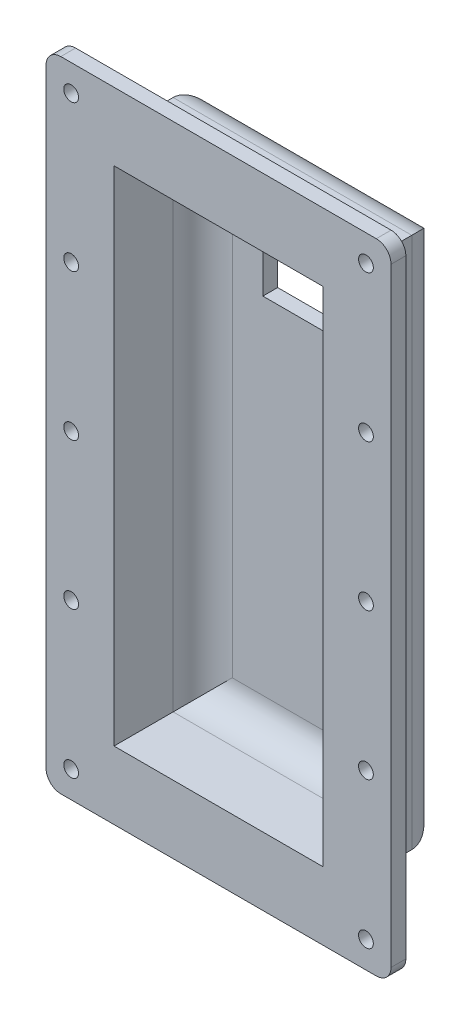
SolidWorks part; units mm, degrees
ref_plane "Front Plane" through (0, 0, 0) normal (0, 0, 1) x (1, 0, 0)
ref_plane "Top Plane" through (0, 0, 0) normal (0, 1, 0) x (1, 0, 0)
ref_plane "Right Plane" through (0, 0, 0) normal (1, 0, 0) x (0, 0, -1)
sketch "Sketch1" plane through (0, 0, 0) normal (0, 0, 1) x (1, 0, 0)
  line L1 (-20.18, 45) -> (20.18, 45)
  line L2 (-20.18, 45) -> (-20.18, -45)
  line L3 (-20.18, -45) -> (20.18, -45)
  line L4 (20.18, 45) -> (20.18, -45)
  line L5 (-20.18, 45) -> (20.18, -45) construction
  line L6 (-20.18, -45) -> (20.18, 45) construction
  point P0 (0, 0)
  dimension "D1" = 40.36
  dimension "D2" = 90
extrude "Boss-Extrude1" add sketch "Sketch1" along normal blind 15
sketch "Sketch2" plane through (0, 0, 15) normal (0, 0, 1) x (1, 0, 0)
  line L0 (-20.18, 45) -> (20.18, 45) construction
  line L1 (-29.18, 54) -> (29.18, 54)
  line L2 (-29.18, 54) -> (-29.18, -54)
  line L3 (-29.18, -54) -> (29.18, -54)
  line L4 (29.18, 54) -> (29.18, -54)
  line L5 (-29.18, 54) -> (29.18, -54) construction
  line L6 (-29.18, -54) -> (29.18, 54) construction
  line L7 (-20.18, 45) -> (-20.18, -45) construction
  point P0 (0, 0)
  point P8 (0, 45)
  dimension "D1" = 9
  dimension "D2" = 9
extrude "Boss-Extrude2" add sketch "Sketch2" along normal blind 2.5
shell "Shell1" thickness 2.5 removed face at (0, 0, 17.5)
fillet "Fillet1" radius 2.5 4 edges at (-29.18, -54, 16.25) (29.18, -54, 16.25) (29.18, 54, 16.25) (-29.18, 54, 16.25)
fillet "Fillet2" radius 5 8 edges at (0, -42.5, 2.5) (17.68, 0, 2.5) (-17.68, 0, 2.5) (0, 42.5, 2.5) (0, -45, 0) (20.18, 0, 0) (0, 45, 0) (-20.18, 0, 0)
sketch "Sketch3" plane through (0, 0, 2.5) normal (0, 0, 1) x (1, 0, 0)
  line L1 (-7.5, 29) -> (7.5, 29)
  line L2 (-7.5, 29) -> (-7.5, 21)
  line L3 (-7.5, 21) -> (7.5, 21)
  line L4 (7.5, 29) -> (7.5, 21)
  line L5 (-7.5, 29) -> (7.5, 21) construction
  line L6 (-7.5, 21) -> (7.5, 29) construction
  point P0 (0, 25)
  dimension "D1" = 8
  dimension "D2" = 15
  dimension "D3" = 25
extrude "Cut-Extrude1" cut sketch "Sketch3" against normal through all
sketch "Sketch4" plane through (0, 0, 17.5) normal (0, 0, 1) x (1, 0, 0)
  line L0 (20.18, 45) -> (20.18, -45) construction
  line L3 (-24.93, -49.5) -> (24.93, -49.5) construction
  line L10 (-24.93, -49.5) -> (-24.93, 49.5) construction
  line L11 (-24.93, 49.5) -> (24.93, 49.5) construction
  line L12 (24.93, -49.5) -> (24.93, 49.5) construction
  line L13 (-24.93, -49.5) -> (24.93, 49.5) construction
  line L14 (-24.93, 49.5) -> (24.93, -49.5) construction
  circle A16 centre (-24.93, 49.5) radius 1.25
  circle A17 centre (24.93, 49.5) radius 1.25
  circle A18 centre (24.93, 24.75) radius 1.25
  circle A19 centre (24.93, 0) radius 1.25
  circle A20 centre (24.93, -24.75) radius 1.25
  circle A21 centre (24.93, -49.5) radius 1.25
  circle A22 centre (-24.93, 24.75) radius 1.25
  circle A23 centre (-24.93, 0) radius 1.25
  circle A24 centre (-24.93, -24.75) radius 1.25
  circle A25 centre (-24.93, -49.5) radius 1.25
  point P0 (0, 0)
  dimension "D1" = 99
  dimension "D3" = 2.5
  dimension "D2" = 4.75
  dimension "D4" = 5
extrude "Cut-Extrude2" cut sketch "Sketch4" against normal up to surface (2.5 mm away) up to face at (0, 0, 15)
equation "\"case_width\"=40.36"
equation "\"D1@Sketch1\"=\"case_width\""
